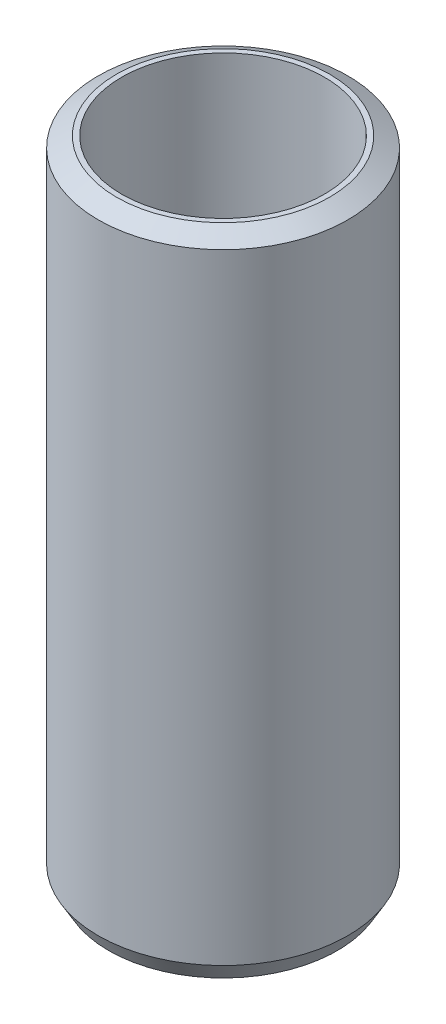
SolidWorks part; units mm, degrees
ref_plane "Front Plane" through (0, 0, 0) normal (0, 0, 1) x (1, 0, 0)
ref_plane "Top Plane" through (0, 0, 0) normal (0, 1, 0) x (1, 0, 0)
ref_plane "Right Plane" through (0, 0, 0) normal (1, 0, 0) x (0, 0, -1)
sketch "Sketch1" plane through (0, 0, 0) normal (0, 1, 0) x (1, 0, 0)
  circle A0 centre (0, 0) radius 40
  dimension "SHAFT_OD" = 80
extrude "Boss-Extrude1" add sketch "Sketch1" along normal blind 207.9229
sketch "Sketch2" plane through (0, 0, 0) normal (0, 1, 0) x (1, 0, 0)
  circle A0 centre (0, 0) radius 32.5014
  dimension "BORE_D" = 65.0028
extrude "Cut-Extrude1" cut sketch "Sketch2" along normal through all
chamfer "Chamfer1" distance 3.3702 angle 60 2 edges at (0, 207.9229, 40) (0, 0, 40) first distance on face at (0, 207.9229, 40) first distance on face at (0, 0, 32.5014)
